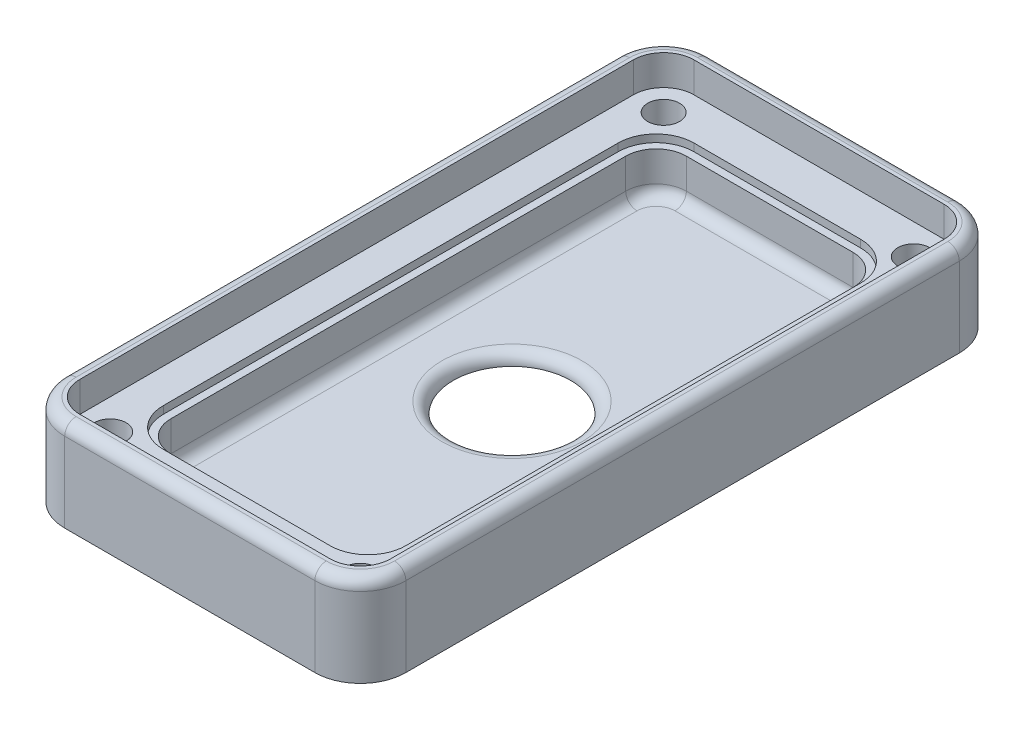
SolidWorks part; units mm, degrees
material "EN8"
ref_plane "Front Plane" through (0, 0, 0) normal (0, 0, 1) x (1, 0, 0)
ref_plane "Top Plane" through (0, 0, 0) normal (0, 1, 0) x (1, 0, 0)
ref_plane "Right Plane" through (0, 0, 0) normal (1, 0, 0) x (0, 0, -1)
sketch "Sketch1" plane through (0, 0, 0) normal (0, 1, 0) x (1, 0, 0)
  line L1 (-16.5, -42.5) -> (16.5, -42.5)
  line L2 (-22.5, -36.5) -> (-22.5, 36.5)
  line L3 (-16.5, 42.5) -> (16.5, 42.5)
  line L4 (22.5, -36.5) -> (22.5, 36.5)
  line L5 (-22.5, -42.5) -> (22.5, 42.5) construction
  line L6 (-22.5, 42.5) -> (22.5, -42.5) construction
  arc A0 (-16.5, -42.5) -> (-22.5, -36.5) centre (-16.5, -36.5) cw
  arc A1 (16.5, -42.5) -> (22.5, -36.5) centre (16.5, -36.5) ccw
  arc A2 (16.5, 42.5) -> (22.5, 36.5) centre (16.5, 36.5) cw
  arc A3 (-22.5, 36.5) -> (-16.5, 42.5) centre (-16.5, 36.5) cw
  point P0 (0, 0)
  dimension "D1" = 6
  dimension "D2" = 85
  dimension "D3" = 45
extrude "Boss-Extrude1" add sketch "Sketch1" along normal blind 12
sketch "Sketch2" plane through (0, 12, 0) normal (0, 1, 0) x (1, 0, 0)
  line L8 (-16.5, -40.5) -> (16.5, -40.5)
  line L9 (20.5, -36.5) -> (20.5, 36.5)
  line L10 (16.5, 40.5) -> (-16.5, 40.5)
  line L11 (-20.5, 36.5) -> (-20.5, -36.5)
  line L12 (-16.5, -40.5) -> (16.5, -40.5)
  line L13 (20.5, -36.5) -> (20.5, 36.5)
  line L14 (16.5, 40.5) -> (-16.5, 40.5)
  line L15 (-20.5, 36.5) -> (-20.5, -36.5)
  arc A8 (-20.5, -36.5) -> (-16.5, -40.5) centre (-16.5, -36.5) ccw
  arc A9 (16.5, -40.5) -> (20.5, -36.5) centre (16.5, -36.5) ccw
  arc A10 (20.5, 36.5) -> (16.5, 40.5) centre (16.5, 36.5) ccw
  arc A11 (-16.5, 40.5) -> (-20.5, 36.5) centre (-16.5, 36.5) ccw
  arc A12 (-20.5, -36.5) -> (-16.5, -40.5) centre (-16.5, -36.5) ccw
  arc A13 (16.5, -40.5) -> (20.5, -36.5) centre (16.5, -36.5) ccw
  arc A14 (20.5, 36.5) -> (16.5, 40.5) centre (16.5, 36.5) ccw
  arc A15 (-16.5, 40.5) -> (-20.5, 36.5) centre (-16.5, 36.5) ccw
  dimension "D1" = 2
extrude "Cut-Extrude1" cut sketch "Sketch2" against normal blind 4
sketch "Sketch3" plane through (0, 0, 0) normal (0, 1, 0) x (1, 0, 0)
  circle A0 centre (0, 0) radius 7.75
  dimension "D1" = 15.5
extrude "Cut-Extrude2" cut sketch "Sketch3" along normal through all
ref_plane "Plane1" through (0, 1.5, 0) normal (0, 1, 0) x (1, 0, 0)
ref_plane "Plane2" through (0, 7, 0) normal (0, -1, 0) x (-1, 0, 0)
sketch "Sketch4" plane through (0, 7, 0) normal (0, 1, 0) x (1, 0, 0)
  line L0 (-16, -30) -> (-16, 30)
  line L1 (-11, -35) -> (11, -35) construction
  line L2 (-16, -30) -> (-16, 30) construction
  line L3 (-11, 35) -> (11, 35) construction
  line L4 (16, -30) -> (16, 30) construction
  line L5 (-16, -35) -> (16, 35) construction
  line L6 (-16, 35) -> (16, -35) construction
  line L7 (-11, 35) -> (11, 35)
  line L8 (16, -30) -> (16, 30)
  line L9 (-11, -35) -> (11, -35)
  arc A0 (-11, -35) -> (-16, -30) centre (-11, -30) cw construction
  arc A1 (11, -35) -> (16, -30) centre (11, -30) ccw construction
  arc A2 (11, 35) -> (16, 30) centre (11, 30) cw construction
  arc A3 (-16, 30) -> (-11, 35) centre (-11, 30) cw construction
  arc A4 (-16, 30) -> (-11, 35) centre (-11, 30) cw
  arc A5 (11, 35) -> (16, 30) centre (11, 30) cw
  arc A6 (11, -35) -> (16, -30) centre (11, -30) ccw
  arc A7 (-11, -35) -> (-16, -30) centre (-11, -30) cw
  point P0 (0, 0)
  dimension "D3" = 5
  dimension "D1" = 32
  dimension "D2" = 70
  dimension "D4" = 0
extrude "Cut-Extrude3" cut sketch "Sketch4" along normal through all
sketch "Sketch6" plane through (0, 1.5, 0) normal (0, 1, 0) x (1, 0, 0)
  line L8 (-11, -34) -> (11, -34)
  line L10 (15, -30) -> (15, 30)
  line L16 (11, 34) -> (-11, 34)
  line L18 (-15, 30) -> (-15, -30)
  line L20 (-11, -34) -> (11, -34)
  line L21 (15, -30) -> (15, 30)
  line L22 (11, 34) -> (-11, 34)
  line L23 (-15, 30) -> (-15, -30)
  arc A12 (-15, -30) -> (-11, -34) centre (-11, -30) ccw
  arc A13 (11, -34) -> (15, -30) centre (11, -30) ccw
  arc A14 (15, 30) -> (11, 34) centre (11, 30) ccw
  arc A15 (-11, 34) -> (-15, 30) centre (-11, 30) ccw
  arc A16 (-15, -30) -> (-11, -34) centre (-11, -30) ccw
  arc A17 (11, -34) -> (15, -30) centre (11, -30) ccw
  arc A18 (15, 30) -> (11, 34) centre (11, 30) ccw
  arc A19 (-11, 34) -> (-15, 30) centre (-11, 30) ccw
  dimension "D1" = 1
extrude "Cut-Extrude4" cut sketch "Sketch6" along normal through all
sketch "Sketch8" plane through (0, 0, 0) normal (0, 1, 0) x (1, 0, 0)
  line L1 (16.5, -36.5) -> (-16.5, -36.5) construction
  line L2 (16.5, -36.5) -> (16.5, 36.5) construction
  line L3 (16.5, 36.5) -> (-16.5, 36.5) construction
  line L4 (-16.5, -36.5) -> (-16.5, 36.5) construction
  line L5 (16.5, -36.5) -> (-16.5, 36.5) construction
  line L6 (16.5, 36.5) -> (-16.5, -36.5) construction
  arc A0 (-16.5, 42.5) -> (-22.5, 36.5) centre (-16.5, 36.5) ccw construction
  point P0 (0, 0)
hole_wizard "Ø4.2 (4.2) Diameter Hole1" positions "Sketch9" profile "Sketch10" hole size "Ø4.2" standard "ANSI Metric" end condition through all
sketch "Sketch9" plane through (0, 0, 0) normal (0, -1, 0) x (1, 0, 0)
  point P0 (-16.5, 36.5)
  point P3 (16.5, 36.5)
  point P6 (16.5, -36.5)
  point P9 (-16.5, -36.5)
sketch "Sketch10" plane through (-16.5, 0, 36.5) normal (1, 0, 0) x (0, 0, -1)
  line L0 (0, 0) -> (0, 12)
  line L1 (0, 12) -> (2.1, 12)
  line L2 (2.1, 12) -> (2.1, 0)
  line L5 (2.1, 0) -> (0, 0)
  line L11 (0, -6.35) -> (0, 107.95) construction
  dimension "Thru Hole Dia." = 4.2
  dimension "Thru Hole Depth" = 12
fillet "Fillet1" radius 1.5 8 edges at (-20.7426, 12, 40.7426) (-22.5, 12, 0) (-20.7426, 12, -40.7426) (0, 12, -42.5) (20.7426, 12, -40.7426) (22.5, 12, 0) (20.7426, 12, 40.7426) (0, 12, 42.5)
fillet "Fillet2" radius 1.5 9 edges at (0, 1.5, 7.75) (-15, 1.5, 0) (-13.8284, 1.5, -32.8284) (0, 1.5, -34) (13.8284, 1.5, -32.8284) (15, 1.5, 0) (13.8284, 1.5, 32.8284) (0, 1.5, 34) (-13.8284, 1.5, 32.8284)
